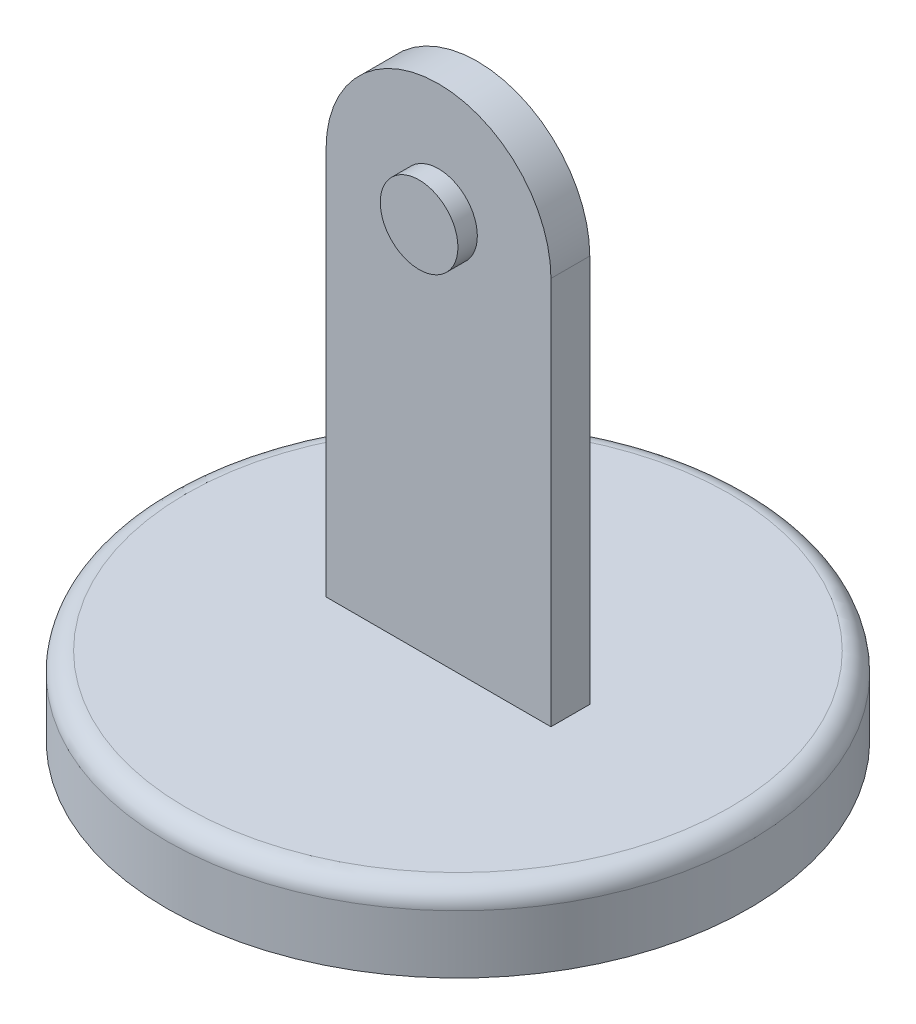
SolidWorks part; units mm, degrees
ref_plane "Front Plane" through (0, 0, 0) normal (0, 0, 1) x (1, 0, 0)
ref_plane "Top Plane" through (0, 0, 0) normal (0, 1, 0) x (1, 0, 0)
ref_plane "Right Plane" through (0, 0, 0) normal (1, 0, 0) x (0, 0, -1)
sketch "Sketch1" plane through (0, 0, 0) normal (0, 1, 0) x (1, 0, 0)
  circle A0 centre (0, 0) radius 75
  dimension "D1" = 150
extrude "Boss-Extrude1" add sketch "Sketch1" along normal blind 20
fillet "Fillet1" radius 5 1 edges at (0, 20, 75)
sketch "Sketch2" plane through (0, 0, 0) normal (0, 0, 1) x (1, 0, 0)
  line L0 (-28.9586, 20) -> (28.9586, 20)
  line L1 (-28.9586, 120) -> (-28.9586, 20)
  line L3 (28.9586, 120) -> (28.9586, 20)
  circle A0 centre (0, 120) radius 28.9586
  dimension "D2" = 100
  dimension "D3" = 100
extrude "Boss-Extrude2" add sketch "Sketch2" along normal blind 5 and the other way blind 5 contours A0 L1 L0 L3 | A0 L1 region at (0, 58.8984, 0) region at (0, 120, 0)
sketch "Sketch3" plane through (0, 0, 0) normal (0, 0, 1) x (1, 0, 0)
  line L0 (0, 0) -> (0, 120)
  circle A0 centre (0, 120) radius 10
  dimension "D2" = 20
  dimension "D1" = 120
extrude "Boss-Extrude4" add sketch "Sketch3" along normal blind 10 contours A0 region at (6.8711, 113.1289, 0)
sketch "Sketch4" plane through (0, 0, 0) normal (0, 0, 1) x (1, 0, 0)
  circle A0 centre (0, 120) radius 5
  dimension "D1" = 10
extrude "Cut-Extrude2" cut sketch "Sketch4" against normal blind 5 and the other way blind 5
